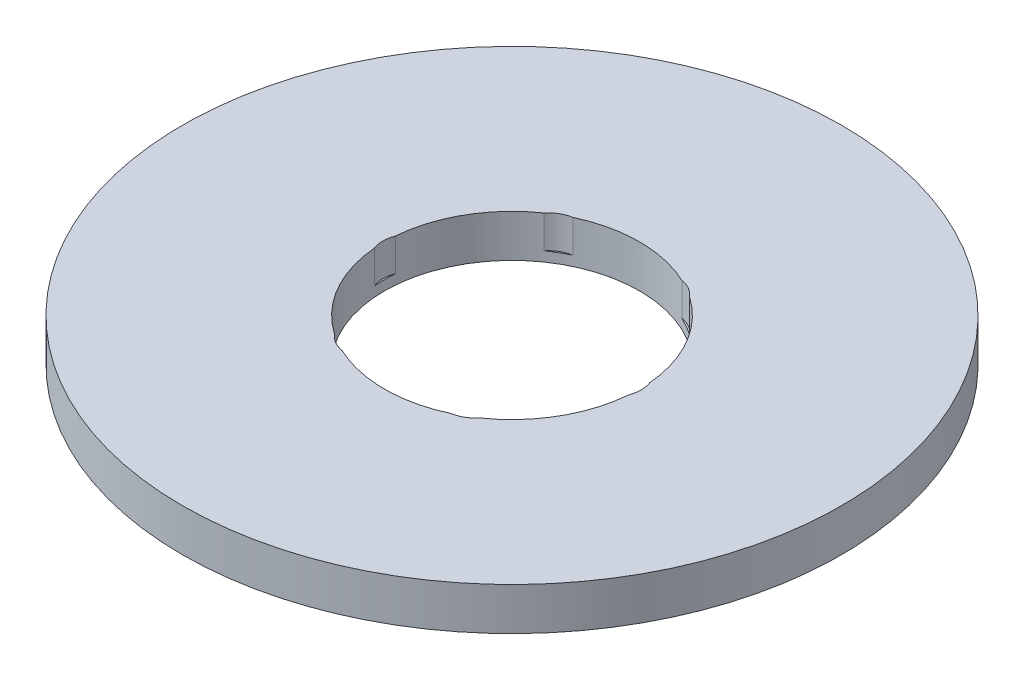
SolidWorks part; units mm, degrees
ref_plane "Front Plane" through (0, 0, 0) normal (0, 0, 1) x (1, 0, 0)
ref_plane "Top Plane" through (0, 0, 0) normal (0, 1, 0) x (1, 0, 0)
ref_plane "Right Plane" through (0, 0, 0) normal (1, 0, 0) x (0, 0, -1)
sketch "Sketch1" plane through (0, 0, 0) normal (0, 1, 0) x (1, 0, 0)
  circle A0 centre (0, 0) radius 77.5
  dimension "FLANGE_OD" = 155
extrude "Boss-Extrude1" add sketch "Sketch1" along normal blind 10
sketch "Sketch2" plane through (0, 0, 0) normal (0, 1, 0) x (1, 0, 0)
  circle A0 centre (0, 0) radius 30
  dimension "BORE_D" = 60
extrude "Cut-Extrude1" cut sketch "Sketch2" along normal through all
sketch "Sketch3" plane through (0, 10, 0) normal (0, 1, 0) x (1, 0, 0)
  circle A0 centre (0, 0) radius 23.3002 construction
  circle A1 centre (-23.3002, 0) radius 7.0523
  dimension "BOLT_D" = 14.1045
  dimension "BOLT_PCD" = 46.6005
extrude "Cut-Extrude2" cut sketch "Sketch3" against normal blind 7.7055
pattern_circular "CirPattern1" count 6 over 360 about axis through (0, 0, 0) along (0, 1, 0) of "Cut-Extrude2"
